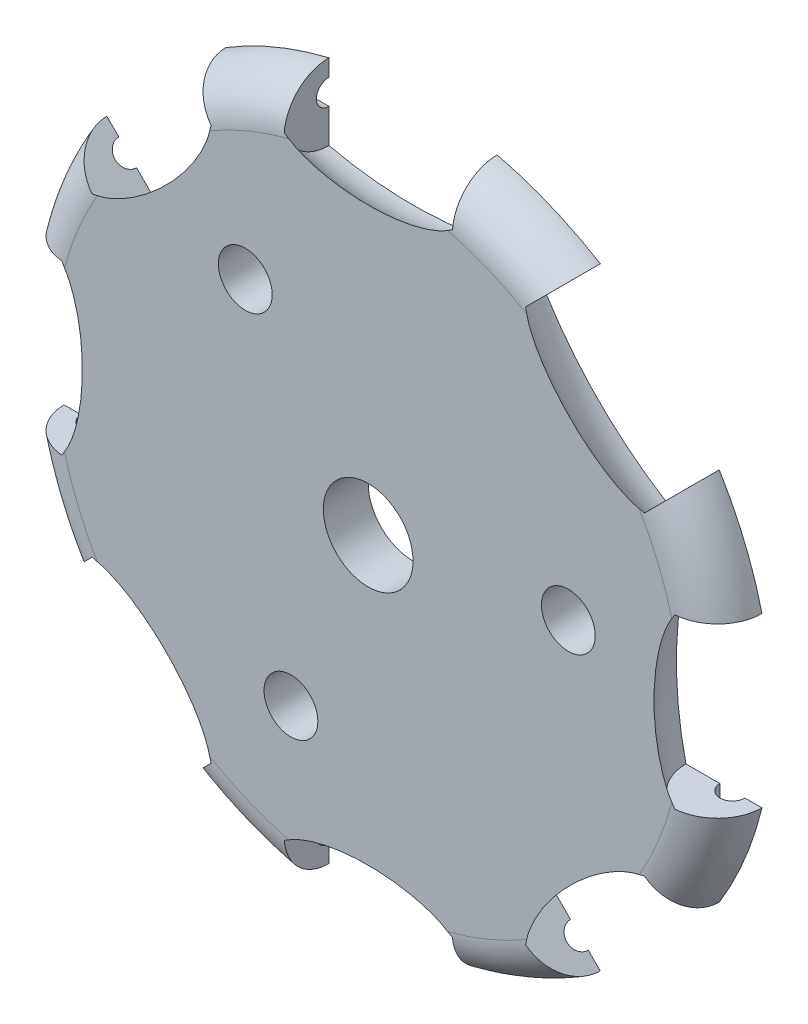
SolidWorks part; units mm, degrees
ref_plane "Front Plane" through (0, 0, 0) normal (0, 0, 1) x (1, 0, 0)
ref_plane "Top Plane" through (0, 0, 0) normal (0, 1, 0) x (1, 0, 0)
ref_plane "Right Plane" through (0, 0, 0) normal (1, 0, 0) x (0, 0, -1)
sketch "Sketch1" plane through (0, 0, 0) normal (0, 0, 1) x (1, 0, 0)
  circle A0 centre (0, 0) radius 25.4
  dimension "D1" = 50.8
extrude "Boss-Extrude1" add sketch "Sketch1" along normal blind 3.175
fillet "Fillet1" radius 3.1852 1 edges at (25.4, 0, 3.175)
sketch "Sketch2" plane through (0, 0, 3.175) normal (0, 0, 1) x (1, 0, 0)
  line L0 (0, 0) -> (-9.7202, -23.4665) construction
  line L1 (0, 0) -> (0, -6.9354) construction
  circle A0 centre (-5.4676, -13.1999) radius 1.905
  circle A1 centre (-8.6977, 11.335) radius 1.905
  circle A2 centre (14.1653, 1.8649) radius 1.905
  circle A3 centre (0, 0) radius 3.175
  circle A4 centre (0, 0) radius 25.4 construction
  point P9 (0, 0)
  dimension "D2" = 3.81
  dimension "D4" = 6.35
  dimension "D1" = 14.2875
  dimension "D5" = 22.5
  dimension "D3" = 3
extrude "Cut-Extrude1" cut sketch "Sketch2" against normal through all
sketch "Sketch5" plane through (0, 0, 0) normal (0, 0, 1) x (1, 0, 0)
  line L0 (-5.9531, 22.606) -> (5.9531, 22.606)
  line L1 (5.9531, 22.606) -> (5.9531, 25.8994)
  line L2 (-5.9531, 22.606) -> (-5.9531, 25.8994)
  line L3 (-5.9531, 22.606) -> (-8.5086, 22.606) construction
  arc A0 (-5.9531, 25.8994) -> (5.9531, 25.8994) centre (0, 0) cw
  circle A1 centre (0, 0) radius 25.4 construction
  point P5 (0, 22.606)
  point P9 (0, 26.5748)
  dimension "D1" = 11.9062
  dimension "D2" = 22.606
  dimension "D3" = 7.9375
revolve "Cut-Revolve1" cut sketch "Sketch5" angle 360 about L3
sketch "Sketch6" plane through (0, 0, 0) normal (1, 0, 0) x (0, 0, -1)
  line L0 (0, -25.4) -> (0, 24.6925) construction
  circle A0 centre (0, 22.606) radius 0.889
  arc A1 (-3.163, 21.6886) -> (0, 19.3126) centre (0, 22.606) ccw construction
  dimension "D1" = 1.778
extrude "Cut-Extrude2" cut sketch "Sketch6" against normal mid plane 15.875
pattern_circular "CirPattern1" count 8 over 360 about axis through (0, 0, 0) along (0, 0, 1) of "Cut-Revolve1", "Cut-Extrude2"
